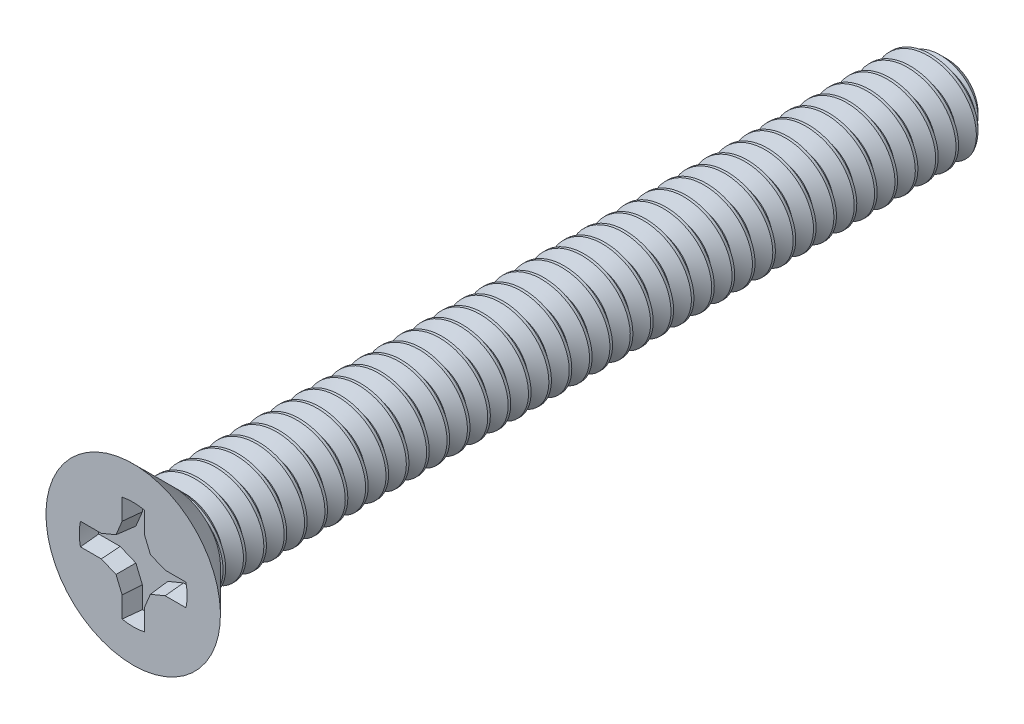
SolidWorks part; units mm, degrees
ref_plane "Front Plane" through (0, 0, 0) normal (0, 0, 1) x (1, 0, 0)
ref_plane "Top Plane" through (0, 0, 0) normal (0, 1, 0) x (1, 0, 0)
ref_plane "Right Plane" through (0, 0, 0) normal (1, 0, 0) x (0, 0, -1)
sketch "Sketch1" plane through (0, 0, 0) normal (1, 0, 0) x (0, 0, -1)
  line L0 (0, 0) -> (-0.96, 0) construction
  line L1 (-0.96, 1.5) -> (-0.96, -1.5) construction
  line L2 (-0.96, 1.5) -> (0, 0.54) construction
  line L3 (-0.96, -1.5) -> (0, -0.54) construction
  line L4 (0, 0.8) -> (0, -0.8) construction
  line L5 (0, 0) -> (13.04, 0) construction
  line L6 (0, 0.8) -> (0.35, 0.8) construction
  line L7 (0, 0.8) -> (-0.26, 0.8) construction
  line L8 (13.04, 0.54) -> (13.04, -0.54) construction
  point P6 (-0.96, 0)
  point P11 (0, 0)
  point P16 (-0.26, 0.8)
  point P17 (11.815, -0.8)
  point P20 (13.04, 0)
  point P21 (-0.48, 0)
  point P22 (11.815, -0.54)
  point P23 (13.04, -0.54)
  point P25 (13.04, 0.54)
  dimension "Head Height" = 0.96
  dimension "Head Diameter" = 3
  dimension "Countersink Angle" = 90
  dimension "Thread OD" = 1.6
  dimension "Length" = 14
  dimension "Thread Pitch" = 0.35
  dimension "D1" = 1.225
sketch "Sketch2" plane through (0, 0, 0) normal (0, 0, 1) x (1, 0, 0)
  line L0 (0.1905, 0.9271) -> (-0.1905, 0.9271) construction
  circle A0 centre (0, 0) radius 0.9271 construction
  point P3 (0, 0.9271)
  point P7 (0, 0.9271)
  dimension "Drive Dia" = 1.8542
  dimension "Drive Width" = 0.381
sketch "Sketch3" plane through (0, 0, 0) normal (1, 0, 0) x (0, 0, -1)
  line L0 (-0.96, 0) -> (-0.96, 1.5)
  line L1 (-0.96, 1.5) -> (-0.26, 0.8)
  line L2 (-0.96, 1.5) -> (0, 0.54) construction
  line L3 (0, 0.8) -> (0.35, 0.8) construction
  line L4 (-0.96, 0) -> (-0.26, 0)
  line L5 (0, 0) -> (-0.96, 0) construction
  line L6 (-0.26, 0) -> (-0.26, 0.8)
revolve "Revolve1" add sketch "Sketch3" angle 360 about L4
sketch "Sketch5" plane through (0, 0, 0) normal (1, 0, 0) x (0, 0, -1)
  line L0 (13.04, 0) -> (-0.26, 0)
  line L1 (0, 0) -> (13.04, 0) construction
  line L2 (-0.26, 0) -> (-0.26, 0.8)
  line L3 (-0.26, 0.8) -> (12.7635, 0.8)
  line L4 (12.7635, 0.8) -> (13.04, 0.5235)
  line L5 (13.04, 0.5235) -> (13.04, 0)
  line L6 (12.7635, 0.8) -> (13.04, 0.8) construction
  line L7 (13.04, 0.8) -> (13.04, 0.5235) construction
  line L8 (0, 0.8) -> (0.35, 0.8) construction
  line L9 (-0.26, -0.8) -> (-0.26, 0.8) construction
  dimension "D1" = 0.2765
revolve "Revolve2" add sketch "Sketch5" angle 360 about L0
sketch "Sketch4" plane through (0, 0, 0.96) normal (0, 0, 1) x (1, 0, 0)
  line L0 (0, 0) -> (0, 0.9271)
  line L1 (0, 0) -> (0.9271, 0)
  line L2 (0, 0) -> (0.5489, 0.5489) construction
  line L3 (0.1905, 0.9073) -> (0.1905, 0.5489)
  line L4 (0.1905, 0.5489) -> (0.1905, 0.1905) construction
  line L5 (0.5489, 0.1905) -> (0.1905, 0.1905) construction
  line L6 (0.9073, 0.1905) -> (0.5489, 0.1905)
  line L7 (0.1905, 0.5489) -> (0.2955, 0.2955)
  line L8 (0.2955, 0.2955) -> (0.5489, 0.1905)
  line L9 (0, 0.9271) -> (0, 1.5) construction
  line L10 (0, 1.5) -> (0, -1.5) construction
  circle A0 centre (0, 0) radius 0.9271 construction
  arc A1 (0, 0.9271) -> (0.1905, 0.9073) centre (0, 0) cw
  arc A2 (0.9271, 0) -> (0.9073, 0.1905) centre (0, 0) ccw
  arc A3 (0.5489, 0.1905) -> (0.1905, 0.5489) centre (0.5489, 0.5489) cw construction
  circle A4 centre (0, 0) radius 1.5 construction
  point P8 (0.2955, 0.2955)
  point P22 (0, -0.9271)
  point P23 (0, 0.9271)
  dimension "D1" = 0.5729
extrude "Cut-Extrude1" cut sketch "Sketch4" against normal blind 0.32 contours L1 A2 L6 L8 L7 L3 A1 L0
pattern_circular "CirPattern1" count 4 over 360 about axis through (0, 0, 0) along (0, 0, 1) of "Cut-Extrude1"
draft "Draft2" type of draft neutral plane draft angle 5 faces to draft 16 face at (-0.7281, 0.1905, 0.8) face at (-0.4222, 0.243, 0.8) face at (-0.243, 0.4222, 0.8) face at (-0.1905, 0.7281, 0.8) face at (0.1905, 0.7281, 0.8) face at (0.243, 0.4222, 0.8) face at (0.4222, 0.243, 0.8) face at (0.7281, 0.1905, 0.8) face at (0.7281, -0.1905, 0.8) face at (0.4222, -0.243, 0.8) face at (0.243, -0.4222, 0.8) face at (0.1905, -0.7281, 0.8) face at (-0.1905, -0.7281, 0.8) face at (-0.243, -0.4222, 0.8) face at (-0.4222, -0.243, 0.8) face at (-0.7281, -0.1905, 0.8) neutral plane through (0, 0, 0.96) neutral plane normal (0, 0, 1) parameters "D1"=5
ref_plane "Plane1" through (0, 0, 0.26) normal (0, 0, -1) x (-1, 0, 0)
split "Split1" trim tools "Plane1" bodies to split 107 105 resulting bodies 108 109
sketch "Sketch6" plane through (0, 0, -13.04) normal (0, 0, 1) x (1, 0, 0)
  circle A1 centre (0, 0) radius 0.8
  circle A2 centre (0, 0) radius 0.8
  dimension "D1" = 0
curve "Helix/Spiral1" pitch 0.35 height 14 turns 40
sketch "Sketch7" plane through (0, 0, 0) normal (1, 0, 0) x (0, 0, -1)
  line L0 (13.0181, 0.8379) -> (13.3681, 0.8379) construction
  line L1 (13.0181, 0.8379) -> (13.1931, 0.5348) construction
  line L2 (13.1931, 0.5348) -> (13.3681, 0.8379) construction
  line L3 (13.1712, 0.5727) -> (13.215, 0.5727) construction
  line L4 (13.04, 0.8) -> (13.3463, 0.8) construction
  line L5 (13.1931, 0.8) -> (13.1931, 0.8379) construction
  line L6 (13.1931, 0.5727) -> (13.1931, 0.5348) construction
  line L7 (13.1931, 0.8189) -> (13.0291, 0.8189) construction
  line L10 (13.215, 0.5727) -> (13.1712, 0.5727)
  line L11 (13.0291, 0.8189) -> (13.1712, 0.5727)
  line L12 (13.0291, 0.8189) -> (13.3572, 0.8189)
  line L13 (13.3572, 0.8189) -> (13.215, 0.5727)
  dimension "D1" = 0.35
  dimension "D2" = 0.0437
sweep "Cut-Sweep1" cut profiles "Sketch7" path "Helix/Spiral1"
combine bodies "Combine1" operation type add bodies to combine 109 110
ref_plane "Plane2" through (0, 0, 0.26) normal (0, 0, 1) x (1, 0, 0)
sketch "Sketch8" plane through (0, 0, 0.26) normal (0, 0, 1) x (1, 0, 0)
  circle A0 centre (0, 0) radius 0.8
extrude "Boss-Extrude1" add sketch "Sketch8" against normal up to vertex (0.26 mm away) draft 45 up to point (0, 0.54, 0)
equation "\"D1@Sketch5\" = \"Thread Pitch@Sketch1\" * .79"
equation "\"D4@Helix/Spiral1\" = \"Thread Pitch@Sketch1\""
equation "\"D3@Helix/Spiral1\"=\"Length@Sketch1\""
equation "\"D1@Sketch7\" = \"Thread Pitch@Sketch1\""
equation "\"D2@Sketch7\" = \"Thread Pitch@Sketch1\" / 8"
equation "\"D1@Sketch1\"=\"Thread Pitch@Sketch1\"*3.5"
equation "\"D1@Cut-Extrude1\"=\"Head Height@Sketch1\"/3"
